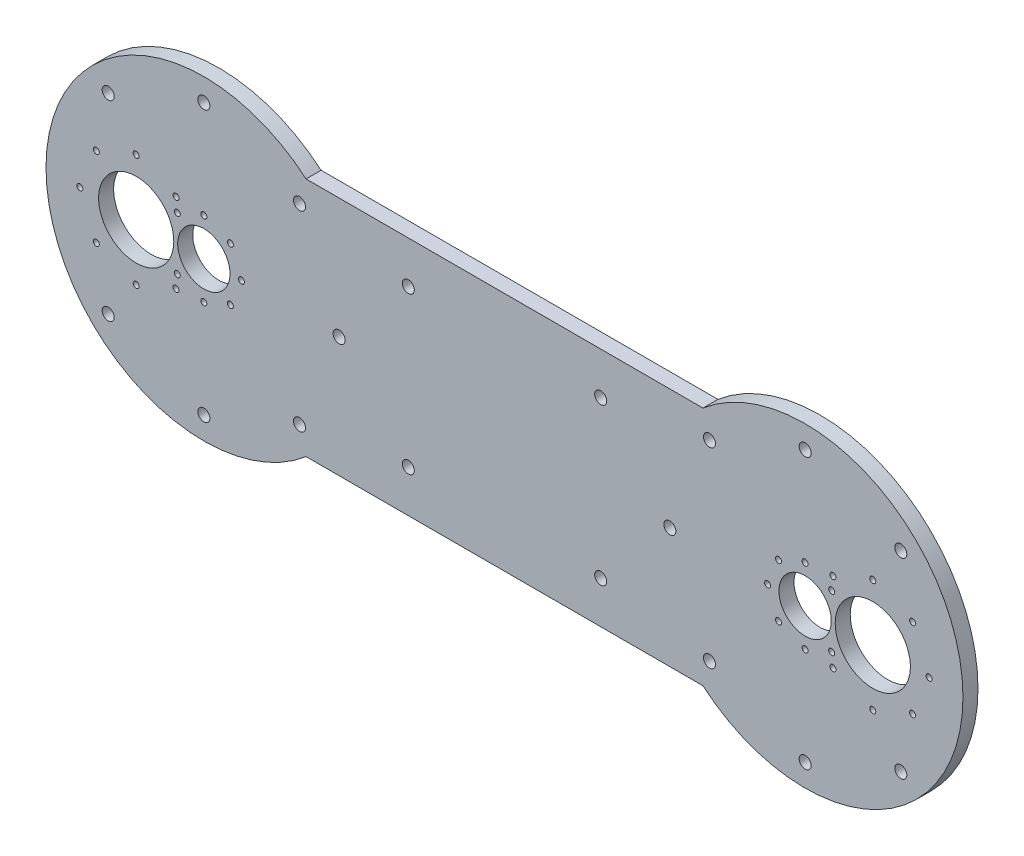
SolidWorks part; units mm, degrees
material "ABS"
ref_plane "Front Plane" through (0, 0, 0) normal (0, 0, 1) x (1, 0, 0)
ref_plane "Top Plane" through (0, 0, 0) normal (0, 1, 0) x (1, 0, 0)
ref_plane "Right Plane" through (0, 0, 0) normal (1, 0, 0) x (0, 0, -1)
sketch "Sketch1" plane through (0, 0, 0) normal (0, 0, 1) x (1, 0, 0)
  line L0 (-87.4716, -41.275) -> (87.4716, -41.275) construction
  line L1 (-83.8153, 50.8) -> (83.8153, 50.8)
  line L2 (-87.4716, 41.275) -> (87.4716, 41.275) construction
  line L3 (-83.8153, -50.8) -> (83.8153, -50.8)
  line L4 (0, 0) -> (0, 100.7987) construction
  arc A0 (-87.4716, 41.275) -> (-87.4716, -41.275) centre (-127, 0) ccw construction
  arc A1 (87.4716, -41.275) -> (87.4716, 41.275) centre (127, 0) ccw construction
  circle A2 centre (-127, 0) radius 3.175
  circle A3 centre (127, 0) radius 3.175
  arc A4 (-83.8153, 50.8) -> (-83.8153, -50.8) centre (-127, 0) ccw
  arc A5 (83.8153, -50.8) -> (83.8153, 50.8) centre (127, 0) ccw
  circle A6 centre (-127, 57.15) radius 2.54
  circle A7 centre (-86.5888, 40.4112) radius 2.54
  circle A8 centre (-69.85, 0) radius 2.54
  circle A9 centre (-86.5888, -40.4112) radius 2.54
  circle A10 centre (-127, -57.15) radius 2.54
  circle A11 centre (-167.4112, -40.4112) radius 2.54
  circle A12 centre (-184.15, 0) radius 2.54 [skipped]
  circle A13 centre (-167.4112, 40.4112) radius 2.54
  circle A14 centre (127, 57.15) radius 2.54
  circle A15 centre (167.4112, 40.4112) radius 2.54
  circle A16 centre (167.4112, -40.4112) radius 2.54
  circle A17 centre (127, -57.15) radius 2.54
  circle A18 centre (86.5888, -40.4112) radius 2.54
  circle A19 centre (69.85, 0) radius 2.54
  circle A20 centre (86.5888, 40.4112) radius 2.54
  point P0 (0, 0)
  dimension "D3" = 6.35
  dimension "D4" = 6.35
  dimension "D6" = 133.35
  dimension "D7" = 133.35
  dimension "D2" = 5.08
  dimension "D5" = 8
  dimension "D1" = 9.525
extrude "Boss-Extrude1" add sketch "Sketch1" along normal mid plane 6.35
sketch "Sketch2" plane through (0, 0, 3.175) normal (0, 0, 1) x (1, 0, 0)
  line L0 (-127, 0) -> (-207.737, 0) construction
  line L4 (0, 0) -> (0, 93.9723) construction
  circle A0 centre (-127, 0) radius 11.049
  circle A1 centre (-155.575, 0) radius 15.875
  circle A2 centre (127, 0) radius 15.875 construction
  circle A3 centre (155.575, 0) radius 23.8125 construction
  circle A4 centre (-155.575, 0) radius 23.8125 construction
  circle A5 centre (-127, 0) radius 15.875 construction
  circle A6 centre (-155.575, 23.8125) radius 1.27
  circle A7 centre (-138.737, 16.838) radius 1.27
  circle A8 centre (-131.7625, 0) radius 1.27 [skipped]
  circle A9 centre (-138.737, -16.838) radius 1.27
  circle A10 centre (-155.575, -23.8125) radius 1.27
  circle A11 centre (-172.413, -16.838) radius 1.27
  circle A12 centre (-179.3875, 0) radius 1.27
  circle A13 centre (-172.413, 16.838) radius 1.27
  circle A14 centre (-127, 15.875) radius 1.27
  circle A15 centre (-115.7747, 11.2253) radius 1.27
  circle A16 centre (-111.125, 0) radius 1.27
  circle A17 centre (-115.7747, -11.2253) radius 1.27
  circle A18 centre (-127, -15.875) radius 1.27
  circle A19 centre (-138.2253, -11.2253) radius 1.27
  circle A20 centre (138.2253, 11.2253) radius 1.27
  circle A21 centre (-138.2253, 11.2253) radius 1.27
  circle A22 centre (-142.875, 0) radius 1.27 [skipped]
  circle A23 centre (138.2253, -11.2253) radius 1.27
  circle A24 centre (127, -15.875) radius 1.27
  circle A25 centre (115.7747, -11.2253) radius 1.27
  circle A26 centre (111.125, 0) radius 1.27
  circle A27 centre (115.7747, 11.2253) radius 1.27
  circle A28 centre (127, 15.875) radius 1.27
  circle A29 centre (172.413, 16.838) radius 1.27
  circle A30 centre (179.3875, 0) radius 1.27
  circle A31 centre (172.413, -16.838) radius 1.27
  circle A32 centre (155.575, -23.8125) radius 1.27
  circle A33 centre (138.737, -16.838) radius 1.27
  circle A34 centre (138.737, 16.838) radius 1.27
  circle A35 centre (155.575, 23.8125) radius 1.27
  circle A36 centre (155.575, 0) radius 15.875
  circle A37 centre (127, 0) radius 11.049
  dimension "D2" = 28.575
  dimension "D3" = 31.75
  dimension "D4" = 31.75
  dimension "D5" = 47.625
  dimension "D6" = 2.54
  dimension "D1" = 22.098
  dimension "D8" = 2.54
  dimension "D7" = 8
  dimension "D9" = 8
extrude "Cut-Extrude1" cut sketch "Sketch2" against normal through all
sketch "Sketch3" plane through (0, 0, 3.175) normal (0, 0, 1) x (1, 0, 0)
  line L1 (-40.64, 33.02) -> (40.64, 33.02) construction
  line L2 (-40.64, 33.02) -> (-40.64, -33.02) construction
  line L3 (-40.64, -33.02) -> (40.64, -33.02) construction
  line L4 (40.64, 33.02) -> (40.64, -33.02) construction
  line L5 (-40.64, 33.02) -> (40.64, -33.02) construction
  line L6 (-40.64, -33.02) -> (40.64, 33.02) construction
  circle A0 centre (-40.64, 33.02) radius 2.54
  circle A1 centre (40.64, 33.02) radius 2.54
  circle A2 centre (40.64, -33.02) radius 2.54
  circle A3 centre (-40.64, -33.02) radius 2.54
  point P0 (0, 0)
  dimension "D3" = 5.08
  dimension "D4" = 5.08
  dimension "D5" = 5.08
  dimension "D6" = 5.08
  dimension "D1" = 81.28
  dimension "D2" = 66.04
extrude "Cut-Extrude2" cut sketch "Sketch3" against normal through all
